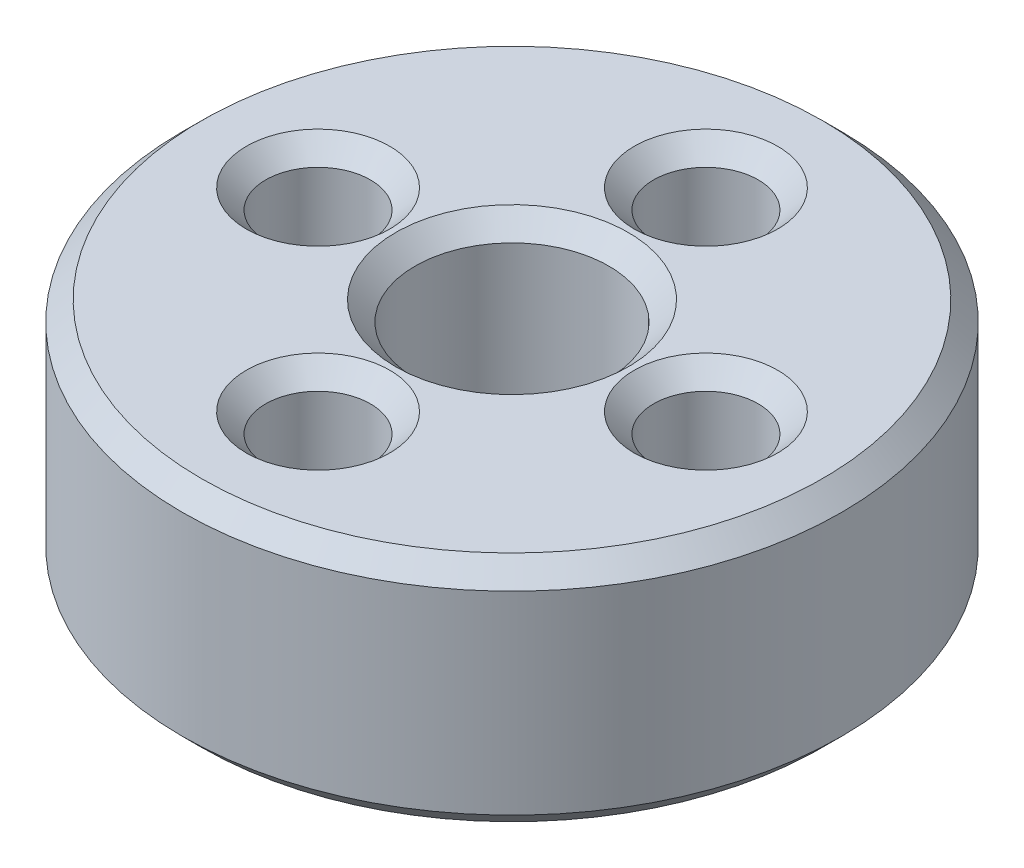
SolidWorks part; units mm, degrees
ref_plane "前视基准面" through (0, 0, 0) normal (0, 0, 1) x (1, 0, 0)
ref_plane "上视基准面" through (0, 0, 0) normal (0, 1, 0) x (1, 0, 0)
ref_plane "右视基准面" through (0, 0, 0) normal (1, 0, 0) x (0, 0, -1)
sketch "草图1" plane through (0, 0, 0) normal (0, 1, 0) x (1, 0, 0)
  line L0 (0, 0) -> (-5.9584, 0) construction
  circle A1 centre (0, 0) radius 8.5
  circle A6 centre (0, 0) radius 5 construction
  circle A7 centre (-5, 0) radius 1.35
  circle A8 centre (0, 5) radius 1.35
  circle A9 centre (5, 0) radius 1.35
  circle A10 centre (0, -5) radius 1.35
  circle A12 centre (0, 0) radius 2.5
  point P1 (0, 0)
  point P15 (0, 0)
  point P25 (0, 0)
  point P61 (0, 0)
  dimension "D2" = 17
  dimension "D6" = 10
  dimension "D7" = 2.7
  dimension "D9" = 5
extrude "凸台-拉伸1" add sketch "草图1" along normal blind 6
chamfer "倒角1" distance 0.5 angle 45 12 edges at (0, 0, 6.35) (5, 0, 1.35) (0, 0, -3.65) (0, 0, 2.5) (-5, 0, 1.35) (0, 0, 8.5) (0, 6, 6.35) (0, 6, -3.65) (-5, 6, 1.35) (0, 6, 8.5) (0, 6, 2.5) (5, 6, 1.35)
